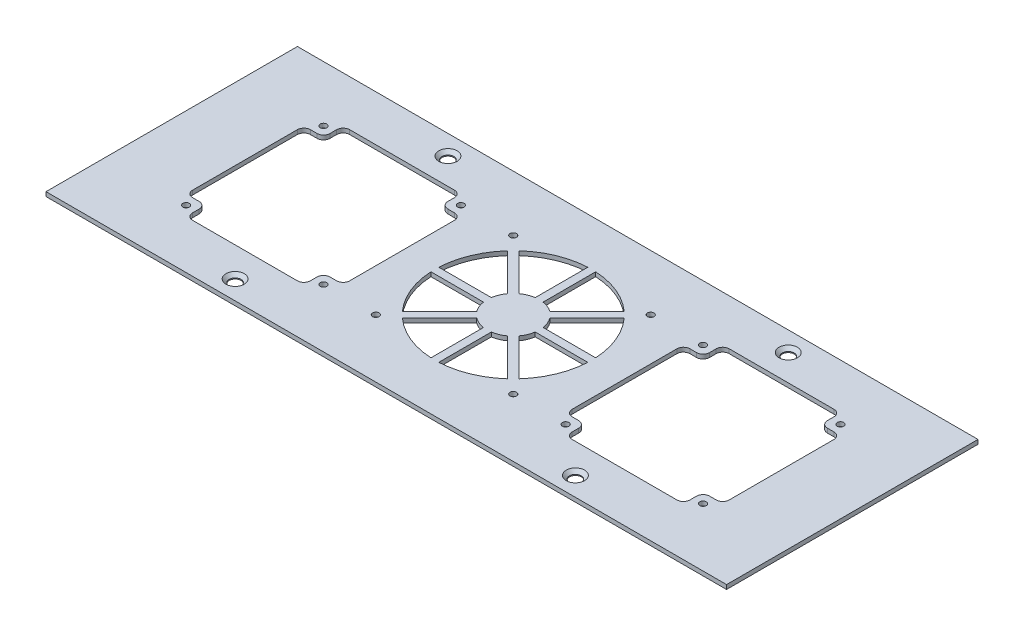
SolidWorks part; units mm, degrees
note: The reader was unsure of these and kept them because the rebuilt part matched: thickness of "Base-Flange1", "Sheet-Metal1", "Sheet-Metal2", "Sheet-Metal3", "Sheet-Metal4".
material "5052-H32"
ref_plane "Front Plane" through (0, 0, 0) normal (0, 0, 1) x (1, 0, 0)
ref_plane "Top Plane" through (0, 0, 0) normal (0, 1, 0) x (1, 0, 0)
ref_plane "Right Plane" through (0, 0, 0) normal (1, 0, 0) x (0, 0, -1)
sketch "Sketch1" plane through (0, 0, 0) normal (0, 1, 0) x (1, 0, 0)
  line L1 (-260, 95.075) -> (260, 95.075)
  line L2 (-260, 95.075) -> (-260, -97.045)
  line L3 (-260, -97.045) -> (260, -97.045)
  line L4 (260, 95.075) -> (260, -97.045)
  point P0 (0, 0)
  dimension "D1" = 520
  dimension "D2" = 192.12
base flange "Base-Flange1" sketch "Sketch1" thickness 3.26 reverse thickness direction no parameters "D1"=1.016
sketch "Sketch2" plane through (0, 0, 0) normal (0, 1, 0) x (1, 0, 0)
  circle A0 centre (130, 80.075) radius 4.5
  circle A1 centre (130, -82.545) radius 4.5
  circle A2 centre (-130, 80.075) radius 4.5
  circle A3 centre (-130, -82.545) radius 4.5
  point P0 (0, 0)
  dimension "D1" = 9
extrude "Cut-Extrude1" cut sketch "Sketch2" against normal blind 10
sketch "Sketch3" plane through (0, 0, 0) normal (0, 1, 0) x (1, 0, 0)
  line L0 (-52.5, -52.5) -> (-52.5, 52.5) construction
  line L1 (52.5, 52.5) -> (-52.5, 52.5) construction
  line L2 (52.5, -52.5) -> (52.5, 52.5) construction
  line L3 (52.5, -52.5) -> (-52.5, -52.5) construction
  line L4 (0, 60) -> (0, -60) construction
  line L5 (-3, -59.925) -> (-3, -19.7737)
  line L6 (-60, 0) -> (60, 0) construction
  line L7 (-3, 59.925) -> (-3, 19.7737)
  line L8 (-19.7737, 3) -> (-59.925, 3)
  line L9 (-19.7737, -3) -> (-59.925, -3)
  line L10 (-44.4947, 40.252) -> (-16.1035, 11.8608)
  line L11 (-52.5, 52.5) -> (0, 0) construction
  line L12 (-40.252, 44.4947) -> (-11.8608, 16.1035)
  line L13 (-44.4947, -40.252) -> (-16.1035, -11.8608)
  line L14 (-40.252, -44.4947) -> (-11.8608, -16.1035)
  line L15 (3, -59.925) -> (3, -19.7737)
  line L16 (40.252, -44.4947) -> (11.8608, -16.1035)
  line L17 (44.4947, -40.252) -> (16.1035, -11.8608)
  line L18 (19.7737, -3) -> (59.925, -3)
  line L19 (19.7737, 3) -> (59.925, 3)
  line L20 (44.4947, 40.252) -> (16.1035, 11.8608)
  line L21 (40.252, 44.4947) -> (11.8608, 16.1035)
  line L22 (3, 59.925) -> (3, 19.7737)
  circle A0 centre (-52.5, 52.5) radius 2.5
  circle A1 centre (52.5, 52.5) radius 2.5
  circle A2 centre (52.5, -52.5) radius 2.5
  circle A3 centre (-52.5, -52.5) radius 2.5
  arc A4 (-40.252, 44.4947) -> (-3, 59.925) centre (0, 0) cw
  arc A5 (-16.1035, 11.8608) -> (-19.7737, 3) centre (0, 0) ccw
  arc A6 (-11.8608, -16.1035) -> (-3, -19.7737) centre (0, 0) ccw
  arc A7 (-59.925, 3) -> (-44.4947, 40.252) centre (0, 0) cw
  arc A8 (-3, -59.925) -> (-40.252, -44.4947) centre (0, 0) cw
  arc A9 (-19.7737, -3) -> (-16.1035, -11.8608) centre (0, 0) ccw
  arc A10 (-3, 19.7737) -> (-11.8608, 16.1035) centre (0, 0) ccw
  arc A11 (-44.4947, -40.252) -> (-59.925, -3) centre (0, 0) cw
  arc A12 (3, -59.925) -> (40.252, -44.4947) centre (0, 0) ccw
  arc A13 (44.4947, -40.252) -> (59.925, -3) centre (0, 0) ccw
  arc A14 (59.925, 3) -> (44.4947, 40.252) centre (0, 0) ccw
  arc A15 (40.252, 44.4947) -> (3, 59.925) centre (0, 0) ccw
  arc A16 (3, 19.7737) -> (11.8608, 16.1035) centre (0, 0) cw
  arc A17 (16.1035, 11.8608) -> (19.7737, 3) centre (0, 0) cw
  arc A18 (19.7737, -3) -> (16.1035, -11.8608) centre (0, 0) cw
  arc A19 (11.8608, -16.1035) -> (3, -19.7737) centre (0, 0) cw
  dimension "D1" = 40
  dimension "D4" = 60
  dimension "D6" = 5
  dimension "D2" = 3
  dimension "D3" = 3
  dimension "D5" = 105
  dimension "D7" = 45
  dimension "D8" = 7.425
  dimension "D9" = 3
  dimension "D10" = 3
extrude "Cut-Extrude2" cut sketch "Sketch3" against normal blind 10 normal cut yes
sketch "Sketch4" plane through (0, 0, 0) normal (0, 1, 0) x (1, 0, 0)
  line L0 (0, -97.045) -> (0, 95.075) construction
  line L1 (-100, 60) -> (-190, 60)
  line L2 (-190, 60) -> (-190, 45)
  line L3 (-190, 45) -> (-205, 45)
  line L4 (-205, 45) -> (-205, -45)
  line L5 (-205, -45) -> (-190, -45)
  line L6 (-190, -45) -> (-190, -60)
  line L7 (-260, -97.045) -> (260, -97.045) construction
  line L9 (-190, -60) -> (-100, -60)
  line L10 (-100, -60) -> (-100, -45)
  line L11 (-100, -45) -> (-85, -45)
  line L12 (-85, -45) -> (-85, 45)
  line L13 (-85, 45) -> (-100, 45)
  line L14 (-100, 45) -> (-100, 60)
  line L15 (92.5, -52.5) -> (197.5, 52.5) construction
  line L16 (-92.5, 52.5) -> (-197.5, 52.5) construction
  line L17 (-92.5, 52.5) -> (-92.5, -52.5) construction
  line L18 (-92.5, -52.5) -> (-197.5, -52.5) construction
  line L19 (-197.5, 52.5) -> (-197.5, -52.5) construction
  line L20 (-92.5, 52.5) -> (-197.5, -52.5) construction
  line L21 (-92.5, -52.5) -> (-197.5, 52.5) construction
  line L22 (92.5, 52.5) -> (197.5, -52.5) construction
  line L23 (197.5, 52.5) -> (197.5, -52.5) construction
  line L24 (92.5, -52.5) -> (197.5, -52.5) construction
  line L25 (92.5, 52.5) -> (92.5, -52.5) construction
  line L26 (92.5, 52.5) -> (197.5, 52.5) construction
  line L27 (100, 45) -> (100, 60)
  line L28 (85, 45) -> (100, 45)
  line L29 (85, -45) -> (85, 45)
  line L30 (100, -45) -> (85, -45)
  line L31 (100, -60) -> (100, -45)
  line L32 (190, -60) -> (100, -60)
  line L33 (190, -45) -> (190, -60)
  line L34 (205, -45) -> (190, -45)
  line L35 (205, 45) -> (205, -45)
  line L36 (190, 45) -> (205, 45)
  line L37 (190, 60) -> (190, 45)
  line L38 (100, 60) -> (190, 60)
  line L39 (260, 95.075) -> (-260, 95.075) construction
  circle A0 centre (-92.5, 52.5) radius 2.5
  circle A1 centre (-197.5, 52.5) radius 2.5
  circle A2 centre (-197.5, -52.5) radius 2.5
  circle A3 centre (-92.5, -52.5) radius 2.5
  circle A4 centre (92.5, -52.5) radius 2.5
  circle A5 centre (197.5, -52.5) radius 2.5
  circle A6 centre (197.5, 52.5) radius 2.5
  circle A7 centre (92.5, 52.5) radius 2.5
  point P0 (-145, 0)
  point P5 (-145, 0)
  point P50 (145, 0)
  dimension "D5" = 5
  dimension "D1" = 145
  dimension "D2" = 120
  dimension "D3" = 15
  dimension "D4" = 105
extrude "Cut-Extrude3" cut sketch "Sketch4" against normal blind 10 normal cut yes
fillet "Fillet2" radius 5 24 edges at (100, -1.63, -60) (190, -1.63, -45) (205, -1.63, -45) (205, -1.63, 45) (190, -1.63, 45) (190, -1.63, 60) (100, -1.63, 60) (100, -1.63, 45) (85, -1.63, 45) (85, -1.63, -45) (100, -1.63, -45) (190, -1.63, -60) (-85, -1.63, -45) (-85, -1.63, 45) (-100, -1.63, 45) (-100, -1.63, 60) (-190, -1.63, 60) (-190, -1.63, 45) (-205, -1.63, 45) (-205, -1.63, -45) (-190, -1.63, -45) (-190, -1.63, -60) (-100, -1.63, -60) (-100, -1.63, -45)
chamfer "Chamfer1" distance 2.5 angle 45 4 edges at (130, 0, -75.575) (130, 0, 87.045) (-130, 0, 87.045) (-130, 0, -75.575)
sketch "Bend-Lines1" [suppressed] plane through (0, 0, 0) normal (0, 1, 0) x (1, 0, 0)
sketch "Bounding-Box1" [suppressed] plane through (0, 0, 0) normal (0, 1, 0) x (1, 0, 0)
sheet metal parameters "Sheet-Metal1" thickness 3.26 parameters "D1"=1.016, "D7"=6.35
flat pattern "Flat-Pattern1" [suppressed]
sketch "Bend-Lines2" plane through (0, 0, 0) normal (0, 1, 0) x (1, 0, 0)
sketch3d "Bounding-Box2" [suppressed]
  line L0 (260, -95, 0) -> (-260, -95, 0) construction
  line L1 (260, 95, 0) -> (-260, 95, 0) construction
  line L2 (260, -95, 0) -> (260, 95, 0) construction
  line L3 (-260, -95, 0) -> (-260, 95, 0) construction
sheet metal parameters "Sheet-Metal2" thickness 3.26 parameters "D1"=1.016, "D7"=6.35
flat pattern "Flat-Pattern1"
sketch "Bend-Lines2" plane through (0, 0, 0) normal (0, 1, 0) x (1, 0, 0)
sketch3d "Bounding-Box2" [suppressed]
  line L0 (260, -95, 0) -> (-260, -95, 0) construction
  line L1 (260, 95, 0) -> (-260, 95, 0) construction
  line L2 (260, -95, 0) -> (260, 95, 0) construction
  line L3 (-260, -95, 0) -> (-260, 95, 0) construction
sheet metal parameters "Sheet-Metal3" thickness 3.26 parameters "D1"=1.016, "D7"=6.35
flat pattern "Flat-Pattern1"
sketch "Bend-Lines2" plane through (0, 0, 0) normal (0, 1, 0) x (1, 0, 0)
sketch3d "Bounding-Box2" [suppressed]
  line L0 (260, -95, 0) -> (-260, -95, 0) construction
  line L1 (260, 95, 0) -> (-260, 95, 0) construction
  line L2 (260, -95, 0) -> (260, 95, 0) construction
  line L3 (-260, -95, 0) -> (-260, 95, 0) construction
sheet metal parameters "Sheet-Metal4" thickness 3.26 parameters "D1"=1.016, "D7"=6.35
flat pattern "Flat-Pattern1"
sketch "Bend-Lines2" plane through (0, 0, 0) normal (0, 1, 0) x (1, 0, 0)
sketch3d "Bounding-Box2" [suppressed]
  line L0 (260, -95, 0) -> (-260, -95, 0) construction
  line L1 (260, 95, 0) -> (-260, 95, 0) construction
  line L2 (260, -95, 0) -> (260, 95, 0) construction
  line L3 (-260, -95, 0) -> (-260, 95, 0) construction
